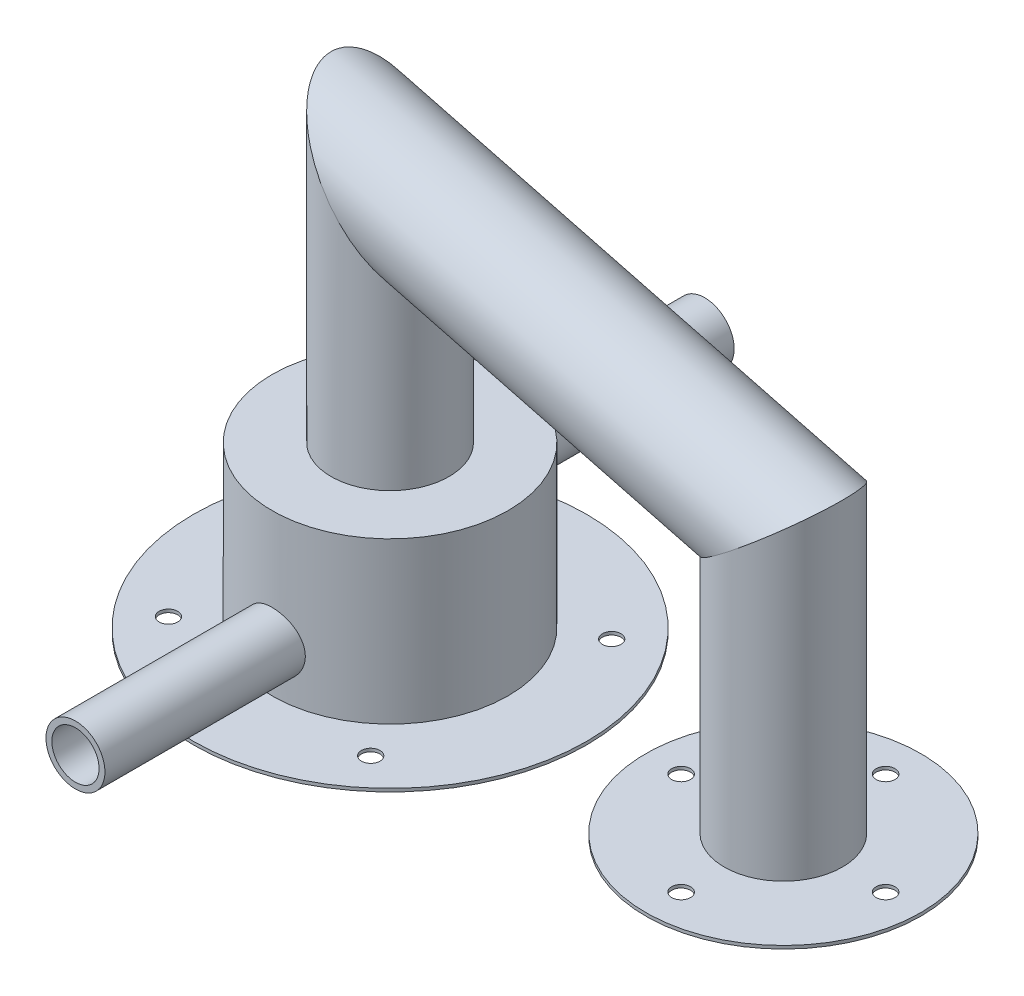
SolidWorks part; units mm, degrees
material "201 Annealed Stainless Steel (SS)"
ref_plane "Front Plane" through (0, 0, 0) normal (0, 0, 1) x (1, 0, 0)
ref_plane "Top Plane" through (0, 0, 0) normal (0, 1, 0) x (1, 0, 0)
ref_plane "Right Plane" through (0, 0, 0) normal (1, 0, 0) x (0, 0, -1)
sketch "Sketch1" plane through (0, 0, 0) normal (0, 0, 1) x (1, 0, 0)
  line L1 (127, -28.5201) -> (127, -121.92) construction
  line L2 (0, -22.4891) -> (0, -127) construction
  line L3 (54.3022, -14.1186) -> (109.2307, -28.4) construction
  line L4 (0, -127) -> (0, 0)
  line L5 (0, 0) -> (127, -33.02)
  line L6 (127, -33.02) -> (127, -121.92)
  line L7 (0, -127) -> (0, 0) construction
  point P7 (100, 0)
  point P8 (0, 0)
  point P10 (0, 0)
  point P12 (127, -33.02)
  dimension "D1" = 33.02
  dimension "D3" = 127
  dimension "D2" = 127
  dimension "D4" = 88.9
sweep "Sweep1" add path "Sketch1" circular profile diameter 38.1 parameters "D3"=38.1
sketch "Sketch23" plane through (0, -127, 0) normal (0, -1, 0) x (1, 0, 0)
  circle A0 centre (0, 0) radius 63.5
  dimension "D1" = 127
extrude "Boss-Extrude1" add sketch "Sketch23" along normal blind 1.016
sketch "Sketch25" plane through (0, -128.016, 0) normal (0, -1, 0) x (1, 0, 0)
  line L0 (0, 0) -> (0, 63.5) construction
  line L1 (0, 0) -> (61.0697, 0) construction
  line L2 (32.6536, 38.9151) -> (0, 0) construction
  circle A0 centre (32.6536, 38.9151) radius 3
  circle A1 centre (0, 0) radius 63.5 construction
  dimension "D1" = 6
  dimension "D2" = 50
  dimension "D3" = 50.8
extrude "Cut-Extrude1" cut sketch "Sketch25" against normal up to next
pattern_circular "CirPattern1" count 4 over 360 about axis through (0, -127, 0) along (0, 1, 0) of "Cut-Extrude1"
shell "Shell1" thickness 1.016 removed face at (38.9151, -128.016, -35.6536)
sketch "Sketch70" plane through (0, -127, 0) normal (0, 1, 0) x (1, 0, 0)
  circle A0 centre (0, 0) radius 37.084
  circle A1 centre (0, 0) radius 38.1
  dimension "D1" = 74.168
  dimension "D2" = 76.2
extrude "Boss-Extrude3" add sketch "Sketch70" along normal blind 50.8
ref_plane "Plane1" through (0, 0, -101.6) normal (0, 0, 1) x (1, 0, 0)
sketch "Sketch75" plane through (0, 0, -101.6) normal (0, 0, 1) x (1, 0, 0)
  line L1 (-63.5, -128.016) -> (63.5, -128.016) construction
  circle A0 centre (0, -94.996) radius 9.525
  dimension "D1" = 19.05
  dimension "D2" = 33.02
extrude "Boss-Extrude5" add sketch "Sketch75" along normal up to next
sketch "Sketch76" plane through (0, 0, -101.6) normal (0, 0, -1) x (-1, 0, 0)
  circle A0 centre (0, -94.996) radius 7.62
  dimension "D1" = 15.24
extrude "Cut-Extrude4" cut sketch "Sketch76" against normal up to next
ref_plane "Plane2" through (0, 0, 101.6) normal (0, 0, 1) x (1, 0, 0)
sketch "Sketch77" plane through (0, 0, 101.6) normal (0, 0, 1) x (1, 0, 0)
  line L0 (0, -76.2) -> (0, -127) construction
  line L1 (63.5, -127) -> (-63.5, -127) construction
  circle A0 centre (0, -111.76) radius 9.525
  dimension "D1" = 19.05
  dimension "D2" = 15.24
extrude "Boss-Extrude7" add sketch "Sketch77" against normal up to next
sketch "Sketch78" plane through (0, 0, 101.6) normal (0, 0, 1) x (1, 0, 0)
  circle A0 centre (0, -111.76) radius 7.62
  dimension "D1" = 15.24
extrude "Cut-Extrude5" cut sketch "Sketch78" against normal up to next
sketch "Sketch80" plane through (0, -76.2, 0) normal (0, 1, 0) x (1, 0, 0)
  circle A0 centre (0, 0) radius 38.1
  dimension "D1" = 76.2
extrude "Boss-Extrude8" add sketch "Sketch80" along normal blind 1.016
sketch "Sketch81" plane through (0, -76.2, 0) normal (0, -1, 0) x (1, 0, 0)
  circle A0 centre (0, 0) radius 18.034
  dimension "D1" = 36.068
extrude "Cut-Extrude7" cut sketch "Sketch81" against normal up to next
sketch "Sketch83" plane through (0, -121.92, 0) normal (0, -1, 0) x (1, 0, 0)
  circle A0 centre (127, 0) radius 44.45
  dimension "D1" = 88.9
extrude "Boss-Extrude9" add sketch "Sketch83" against normal blind 1.016 contours A0
sketch "Sketch87" plane through (0, -121.92, 0) normal (0, -1, 0) x (1, 0, 0)
  circle A0 centre (127, 0) radius 6.35
  dimension "D1" = 12.7
extrude "Cut-Extrude8" cut sketch "Sketch87" against normal up to next contours A0
fillet "Fillet1" radius 0.254 1 edges at (127, -120.904, 6.35)
sketch "Sketch88" plane through (0, -121.92, 0) normal (0, -1, 0) x (1, 0, 0)
  line L0 (0, 0) -> (127, 0) construction
  circle A0 centre (127, -33.02) radius 3.048
  dimension "D1" = 6.096
  dimension "D2" = 33.02
extrude "Cut-Extrude9" cut sketch "Sketch88" against normal up to next contours A0
pattern_circular "CirPattern2" count 4 over 360 about axis through (127, -0.5132, 0) along (0, -1, 0) of "Cut-Extrude9"
